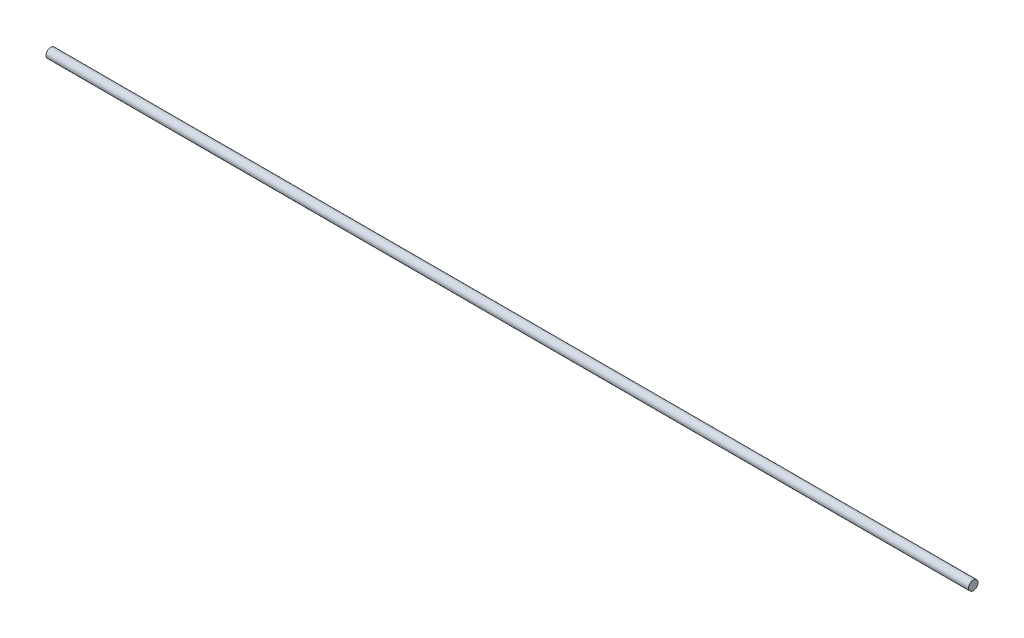
SolidWorks part; units mm, degrees
ref_plane "Front Plane" through (0, 0, 0) normal (0, 0, 1) x (1, 0, 0)
ref_plane "Top Plane" through (0, 0, 0) normal (0, 1, 0) x (1, 0, 0)
ref_plane "Right Plane" through (0, 0, 0) normal (1, 0, 0) x (0, 0, -1)
sketch "Sketch1" plane through (0, 0, 0) normal (1, 0, 0) x (0, 0, -1)
  circle A0 centre (0, 0) radius 3.2
  dimension "D1" = 6.4
extrude "Boss-Extrude1" add sketch "Sketch1" along normal blind 628
